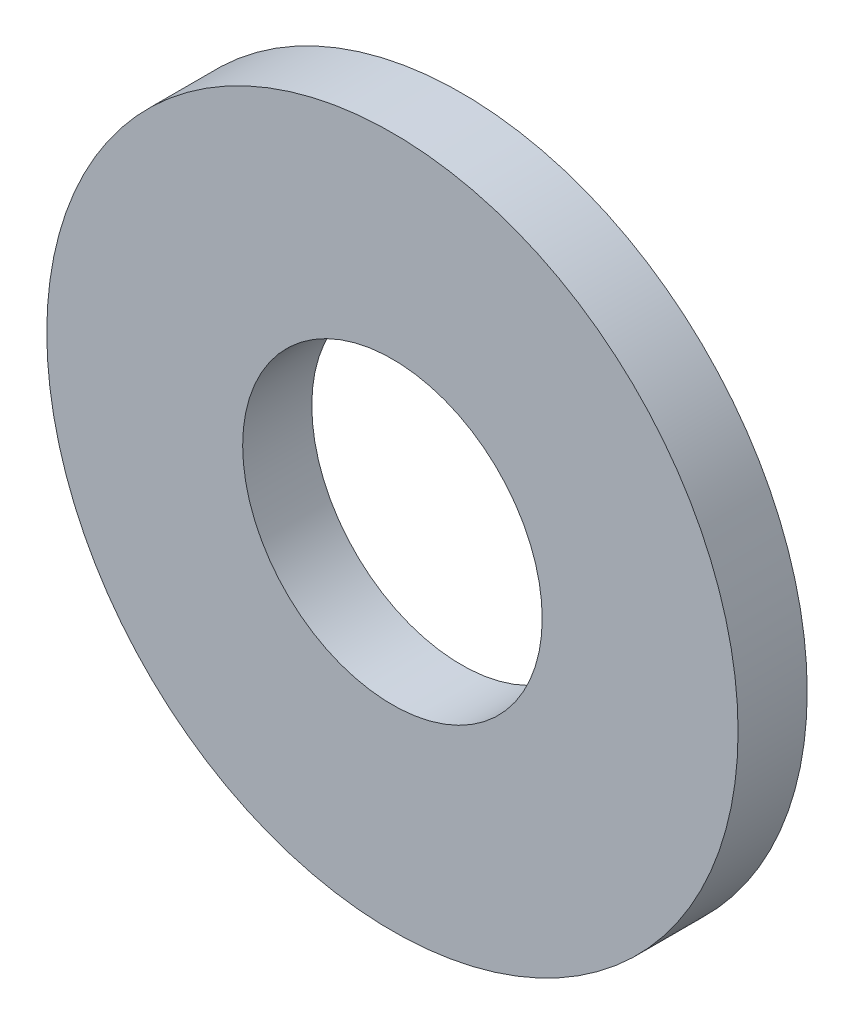
SolidWorks part; units mm, degrees
ref_plane "Front Plane" through (0, 0, 0) normal (0, 0, 1) x (1, 0, 0)
ref_plane "Top Plane" through (0, 0, 0) normal (0, 1, 0) x (1, 0, 0)
ref_plane "Right Plane" through (0, 0, 0) normal (1, 0, 0) x (0, 0, -1)
sketch "Sketch1" plane through (0, 0, 0) normal (0, 0, 1) x (1, 0, 0)
  circle A0 centre (0, 0) radius 6
  circle A1 centre (0, 0) radius 2.6
  dimension "D1" = 12
  dimension "D2" = 5.2
extrude "Boss-Extrude1" add sketch "Sketch1" along normal blind 1.2
